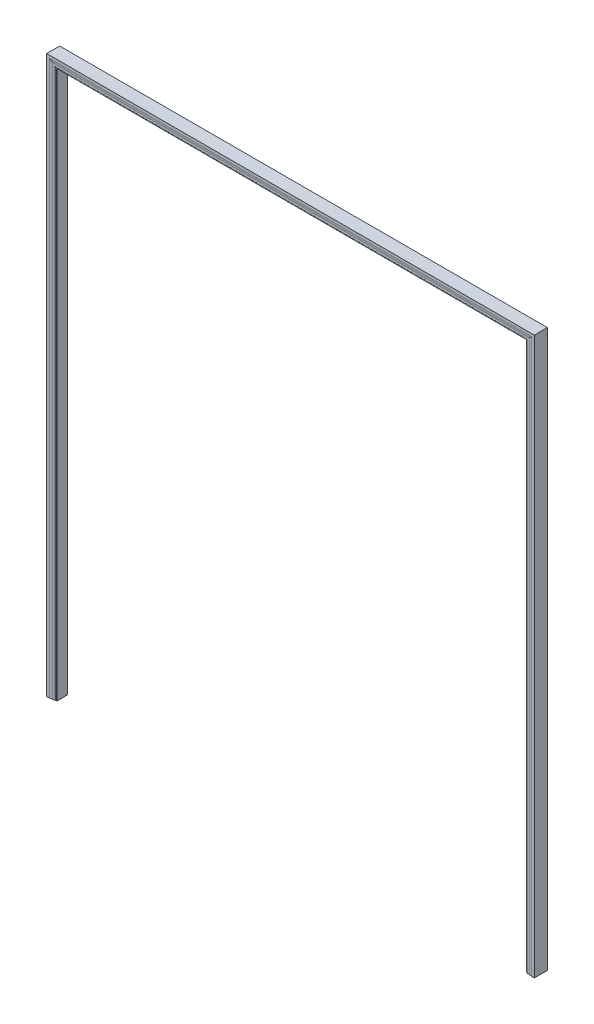
SolidWorks part; units mm, degrees
material "Pine"
ref_plane "Front" through (0, 0, 0) normal (0, 0, 1) x (1, 0, 0)
ref_plane "Top" through (0, 0, 0) normal (0, 1, 0) x (1, 0, 0)
ref_plane "Right" through (0, 0, 0) normal (1, 0, 0) x (0, 0, -1)
sketch "Sketch1" plane through (0, 0, 0) normal (0, 0, 1) x (1, 0, 0)
  line L0 (-935, -1085) -> (-935, 1085)
  line L1 (-900, -1050) -> (900, -1050)
  line L2 (-900, -1050) -> (-900, 1050)
  line L3 (-900, 1050) -> (900, 1050)
  line L4 (900, -1050) -> (900, 1050)
  line L5 (-900, -1050) -> (900, 1050) construction
  line L6 (-900, 1050) -> (900, -1050) construction
  line L7 (-935, 1085) -> (935, 1085)
  line L8 (935, -1085) -> (935, 1085)
  line L9 (-935, -1085) -> (935, -1085)
  point P0 (0, 0)
  dimension "D1" = 2100
  dimension "D2" = 1800
  dimension "D3" = 35
extrude "Boss-Extrude1" add sketch "Sketch1" along normal mid plane 50
sketch "Sketch2" plane through (0, 0, 25) normal (0, 0, 1) x (1, 0, 0)
  line L8 (-905, -1055) -> (905, -1055)
  line L9 (905, -1055) -> (905, 1055)
  line L10 (905, 1055) -> (-905, 1055)
  line L11 (-905, 1055) -> (-905, -1055)
  line L12 (-905, -1055) -> (905, -1055)
  line L13 (905, -1055) -> (905, 1055)
  line L14 (905, 1055) -> (-905, 1055)
  line L15 (-905, 1055) -> (-905, -1055)
  dimension "D1" = 5
extrude "Cut-Extrude2" cut sketch "Sketch2" against normal blind 5
sketch "Sketch3" plane through (0, 0, 25) normal (0, 0, 1) x (1, 0, 0)
  line L8 (912.5, -1062.5) -> (912.5, 1062.5)
  line L9 (-912.5, -1062.5) -> (912.5, -1062.5)
  line L10 (-912.5, 1062.5) -> (-912.5, -1062.5)
  line L11 (912.5, 1062.5) -> (-912.5, 1062.5)
  line L12 (912.5, -1062.5) -> (912.5, 1062.5)
  line L13 (-912.5, -1062.5) -> (912.5, -1062.5)
  line L14 (-912.5, 1062.5) -> (-912.5, -1062.5)
  line L15 (912.5, 1062.5) -> (-912.5, 1062.5)
  dimension "D1" = 7.5
extrude "Cut-Extrude4" cut sketch "Sketch3" against normal blind 2
fillet "Fillet1" radius 1 4 edges at (905, 0, 23) (0, 1055, 23) (-905, 0, 23) (0, -1055, 23)
chamfer "Chamfer1" distance 12 angle 11 4 edges at (0, 1062.5, 25) (912.5, 0, 25) (0, -1062.5, 25) (-912.5, 0, 25) first distance on face at (0, 0, 25)
mirror "Mirror1" about plane through (0, 0, 0) normal (0, 0, 1) of "Cut-Extrude4", "Cut-Extrude2"
fillet "Fillet2" radius 1 4 edges at (-905, 0, -23) (0, -1055, -23) (905, 0, -23) (0, 1055, -23)
chamfer "Chamfer2" distance 12 angle 11 4 edges at (0, 1062.5, -25) (912.5, 0, -25) (-912.5, 0, -25) (0, -1062.5, -25) first distance on face at (0, 0, -25)
sketch "Sketch5" plane through (0, -1085, 0) normal (0, -1, 0) x (1, 0, 0)
  line L1 (-935, 25) -> (935, 25)
  line L2 (-935, 25) -> (-935, -25)
  line L3 (-935, -25) -> (935, -25)
  line L4 (935, 25) -> (935, -25)
extrude "Cut-Extrude5" cut sketch "Sketch5" against normal up to surface (35 mm away) up to face at (0, -1050, 0)
